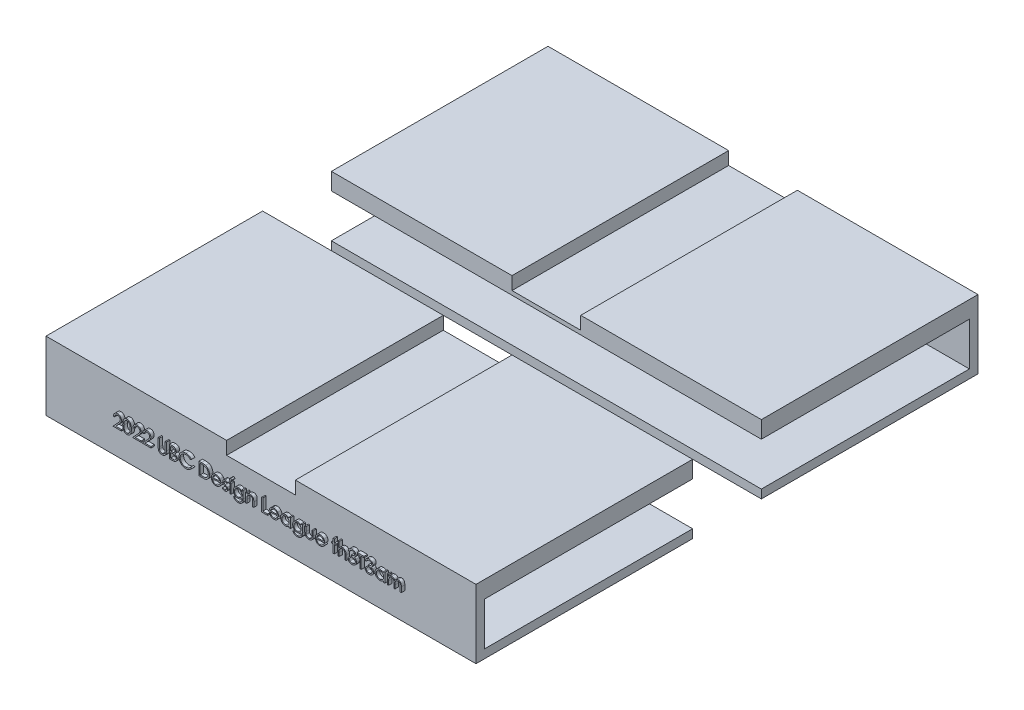
SolidWorks part; units mm, degrees
ref_plane "Front Plane" through (0, 0, 0) normal (0, 0, 1) x (1, 0, 0)
ref_plane "Top Plane" through (0, 0, 0) normal (0, 1, 0) x (1, 0, 0)
ref_plane "Right Plane" through (0, 0, 0) normal (1, 0, 0) x (0, 0, -1)
sketch "Sketch1" plane through (0, 0, 0) normal (0, 1, 0) x (1, 0, 0)
  line L1 (0, 0) -> (250.2, 0)
  line L2 (0, 0) -> (0, 292.1)
  line L3 (0, 292.1) -> (250.2, 292.1)
  line L4 (250.2, 0) -> (250.2, 292.1)
extrude "Boss-Extrude1" add sketch "Sketch1" along normal blind 40
sketch "Sketch2" plane through (0, 0, 0) normal (0, 0, 1) x (1, 0, 0)
  line L0 (0, 40) -> (250.2, 40) construction
  line L1 (105.1, 40) -> (145.1, 40)
  line L2 (105.1, 40) -> (105.1, 32.47)
  line L3 (105.1, 32.47) -> (145.1, 32.47)
  line L4 (145.1, 40) -> (145.1, 32.47)
  dimension "D1" = 40
  dimension "D2" = 7.53
extrude "Cut-Extrude1" cut sketch "Sketch2" against normal through all contours L2 L1 L4 L3
sketch "Sketch3" plane through (250.2, 0, 0) normal (1, 0, 0) x (0, 0, -1)
  line L0 (0, 40) -> (0, 0) construction
  line L1 (5, 30.1056) -> (126.05, 30.1056)
  line L2 (5, 30.1056) -> (5, 5)
  line L3 (5, 5) -> (126.05, 5)
  line L4 (287.1, 30.1056) -> (287.1, 5)
  line L5 (0, 0) -> (292.1, 0) construction
  line L6 (292.1, 40) -> (292.1, 0) construction
  line L7 (0, 40) -> (292.1, 40) construction
  line L8 (126.05, 40) -> (166.05, 40)
  line L9 (126.05, 40) -> (126.05, 30.1056)
  line L10 (126.05, 0) -> (166.05, 0)
  line L11 (166.05, 40) -> (166.05, 30.1056)
  line L13 (126.05, 5) -> (126.05, 0)
  line L14 (166.05, 30.1056) -> (287.1, 30.1056)
  line L15 (166.05, 5) -> (166.05, 0)
  line L16 (166.05, 5) -> (287.1, 5)
  dimension "D1" = 5
  dimension "D2" = 5
  dimension "D3" = 5
extrude "Cut-Extrude3" cut sketch "Sketch3" against normal through all both and the other way through all contours L8 L11 L14 L4 L16 L15 L10 L13 L3 L2 L1 L9
sketch "Sketch4" plane through (0, 0, 0) normal (0, 0, 1) x (1, 0, 0)
  line L0 (0, 16.1161) -> (250.2, 16.1161) construction
  line L1 (0, 40) -> (0, 0) construction
  line L2 (250.2, 40) -> (250.2, 0) construction
  text T0 "2022 UBC Design League th3T3am" font "Century Gothic" height in points 28
extrude "Boss-Extrude2" add sketch "Sketch4" along normal blind 2
